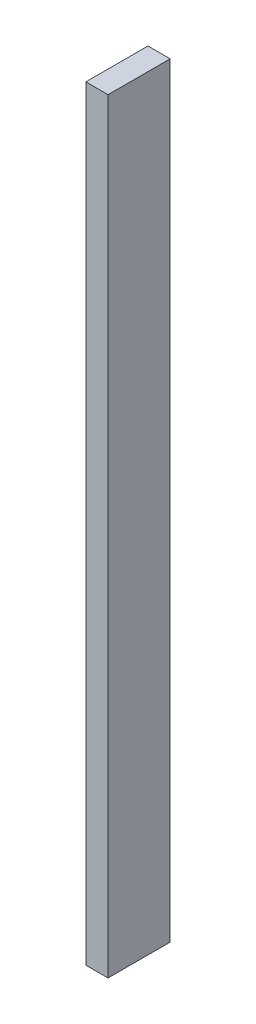
SolidWorks part; units mm, degrees
ref_plane "Front Plane" through (0, 0, 0) normal (0, 0, 1) x (1, 0, 0)
ref_plane "Top Plane" through (0, 0, 0) normal (0, 1, 0) x (1, 0, 0)
ref_plane "Right Plane" through (0, 0, 0) normal (1, 0, 0) x (0, 0, -1)
sketch "Sketch1" plane through (0, 0, 0) normal (0, 1, 0) x (1, 0, 0)
  line L1 (0, 0) -> (3.175, 0)
  line L2 (0, 0) -> (0, 8.89)
  line L3 (0, 8.89) -> (3.175, 8.89)
  line L4 (3.175, 0) -> (3.175, 8.89)
  dimension "D1" = 3.175
  dimension "D2" = 8.89
extrude "Boss-Extrude1" add sketch "Sketch1" along normal blind 109.474
equation "\"D1@Sketch1\"=1/8"
